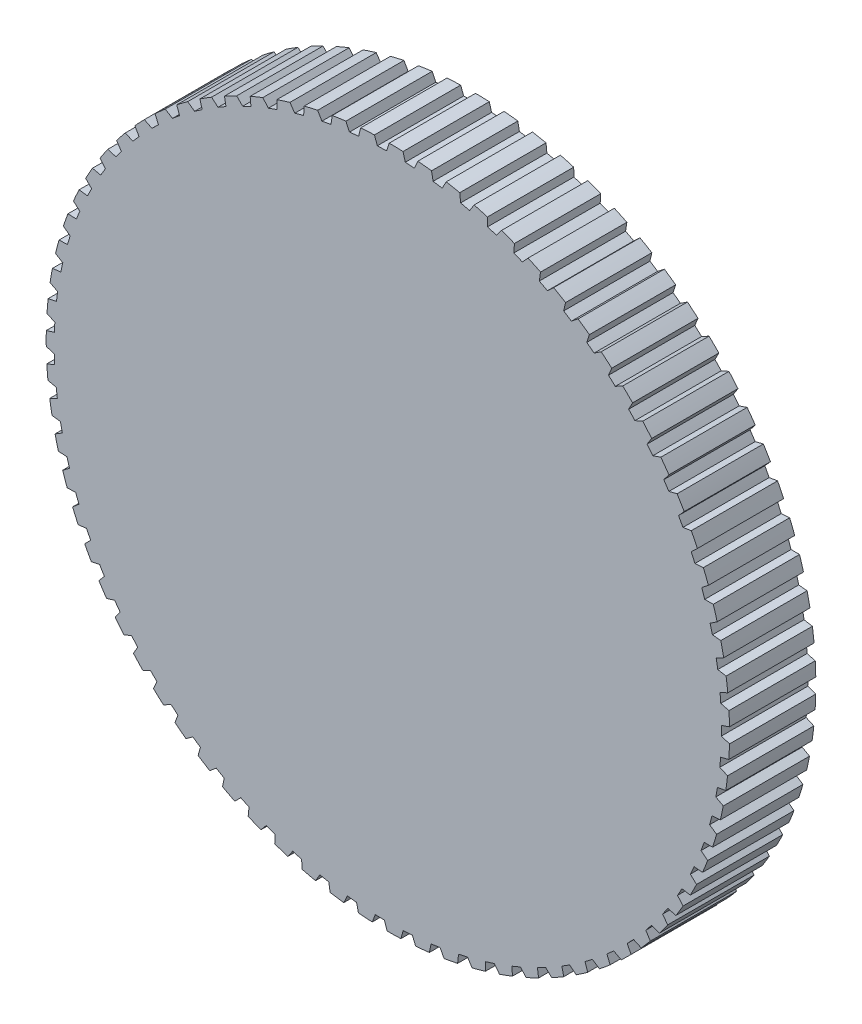
SolidWorks part; units mm, degrees
ref_plane "Ebene vorne" through (0, 0, 0) normal (0, 0, 1) x (1, 0, 0)
ref_plane "Ebene oben" through (0, 0, 0) normal (0, 1, 0) x (1, 0, 0)
ref_plane "Ebene rechts" through (0, 0, 0) normal (1, 0, 0) x (0, 0, -1)
ref_axis "Achse" through (0, 0, 4.125) along (0, 0, -1)
sketch "Skizze1" plane through (0, 0, 0) normal (0, 0, 1) x (1, 0, 0)
  line L0 (0.1158, 29.6998) -> (-0.1158, 28.9998)
  line L1 (1.3154, 29.6709) -> (1.513, 28.9605)
  line L2 (2.3112, 28.9078) -> (2.6006, 29.5859)
  line L3 (2.4559, 29.2468) -> (0, 0) construction
  line L4 (0, 0) -> (0, 29.3498) construction
  line L5 (0.7157, 29.6914) -> (0, 0) construction
  line L6 (1.4142, 29.3157) -> (0, 0) construction
  line L7 (0, 0) -> (1.9123, 28.9369) construction
  line L8 (-0.1158, 28.9998) -> (0, 0)
  line L9 (0, 0) -> (2.3112, 28.9078)
  circle A0 centre (0, 0) radius 29.3498 construction
  arc A1 (0.1158, 29.6998) -> (1.3154, 29.6709) centre (0, 0) cw
  arc A2 (1.513, 28.9605) -> (2.3112, 28.9078) centre (0, 0) cw
  dimension "D1" = 0.7
  dimension "D3" = 1.2
  dimension "D6" = 29
  dimension "D2" = 2.4588
  dimension "D4" = 0.8
  dimension "D5" = 4.8
extrude "Aufsatz-Linear austragen1" add sketch "Skizze1" along normal mid plane 7.5 contours A2 L1 A1 L0 L8 L9 region at (0.7315, 19.5874, 0)
pattern_circular "Kreismuster1" count 75 over 360 about axis through (0, 0, 3.75) along (0, 0, -1) of "Aufsatz-Linear austragen1"
